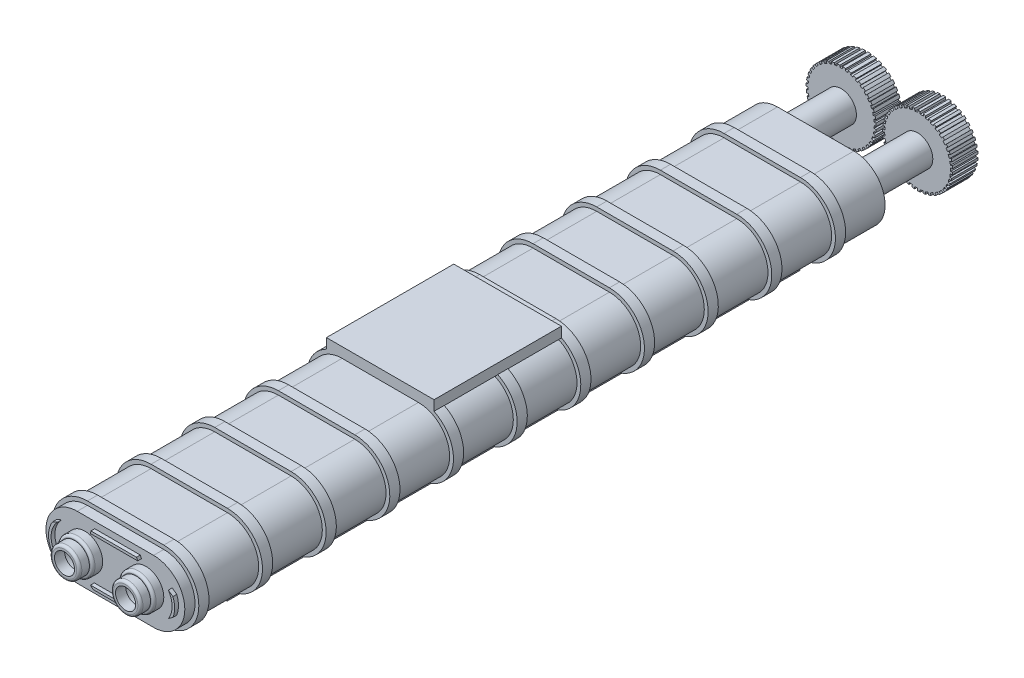
SolidWorks part; units mm, degrees
ref_plane "Front Plane" through (0, 0, 0) normal (0, 0, 1) x (1, 0, 0)
ref_plane "Top Plane" through (0, 0, 0) normal (0, 1, 0) x (1, 0, 0)
ref_plane "Right Plane" through (0, 0, 0) normal (1, 0, 0) x (0, 0, -1)
sketch "Sketch1" plane through (0, 0, 0) normal (0, 0, 1) x (1, 0, 0)
  line L0 (-67.9195, 0) -> (-44.5141, 0) construction
  line L1 (-20, 24.5141) -> (40, 24.5141)
  line L2 (-20, -24.5141) -> (40, -24.5141)
  arc A0 (-20, 24.5141) -> (-20, -24.5141) centre (-20, 0) ccw
  arc A1 (40, -24.5141) -> (40, 24.5141) centre (40, 0) ccw
  dimension "D2" = 49.0283
  dimension "D1" = 60
extrude "Boss-Extrude2" add sketch "Sketch1" along normal mid plane 550
sketch "Sketch4" plane through (0, 0, 0) normal (0, 0, 1) x (1, 0, 0)
  line L0 (27.6992, -24.3343) -> (47.6817, -24.3343)
  line L1 (-27.1587, -24.3343) -> (27.6992, -24.3343)
  line L2 (-27.1587, -24.3343) -> (-27.1587, -27.8343)
  line L3 (-27.1587, -27.8343) -> (27.6992, -27.8343)
  line L4 (47.6817, -24.3343) -> (47.6817, -27.8343)
  line L5 (47.6817, -27.8343) -> (27.6992, -27.8343)
  dimension "D1" = 3.5
extrude "Boss-Extrude3" add sketch "Sketch4" along normal mid plane 450
sketch "Sketch5" plane through (0, 0, -275) normal (0, 0, -1) x (-1, 0, 0)
  circle A0 centre (-40, 0) radius 11.9712
  circle A1 centre (20, 0) radius 11.9712
extrude "Boss-Extrude4" add sketch "Sketch5" along normal blind 50
sketch "Sketch6" plane through (0, 0, -325) normal (0, 0, -1) x (-1, 0, 0)
  circle A0 centre (-40, 0) radius 27.5
  circle A1 centre (20, 0) radius 27.5
  dimension "D1" = 55
  dimension "D2" = 55
extrude "Boss-Extrude5" add sketch "Sketch6" along normal blind 20
sketch "Sketch7" plane through (0, 0, -345) normal (0, 0, -1) x (-1, 0, 0)
  line L1 (-44.5029, 28.9828) -> (-42.0986, 28.9828)
  line L2 (-44.5029, 28.9828) -> (-44.5029, 25.6196)
  line L3 (-44.5029, 25.6196) -> (-42.0986, 25.6196)
  line L4 (-42.0986, 28.9828) -> (-42.0986, 25.6196)
  line L5 (-44.5029, 28.9828) -> (-42.0986, 25.6196) construction
  line L6 (-44.5029, 25.6196) -> (-42.0986, 28.9828) construction
  circle A0 centre (-40, 0) radius 27.5 construction
  point P0 (-43.3007, 27.3012)
extrude "Cut-Extrude1" cut sketch "Sketch7" against normal up to surface (20 mm away) up to face at (12.5, 0, -325)
pattern_circular "CirPattern1" count 39 over 360 about axis through (40, 0, -345) along (0, 0, -1) of "Cut-Extrude1"
sketch "Sketch8" plane through (0, 0, -345) normal (0, 0, -1) x (-1, 0, 0)
  line L1 (19, 29) -> (21, 29)
  line L2 (19, 29) -> (19, 26)
  line L3 (19, 26) -> (21, 26)
  line L4 (21, 29) -> (21, 26)
  line L5 (19, 29) -> (21, 26) construction
  line L6 (19, 26) -> (21, 29) construction
  circle A0 centre (20, 0) radius 27.5 construction
  point P0 (20, 27.5)
  dimension "D1" = 3
  dimension "D2" = 2
extrude "Cut-Extrude2" cut sketch "Sketch8" against normal up to surface (20 mm away) up to face at (-47.5, 0, -325)
pattern_circular "CirPattern2" count 39 over 360 about axis through (-20, 0, -345) along (0, 0, -1) of "Cut-Extrude2"
sketch "Sketch10" plane through (0, 0, 275) normal (0, 0, 1) x (1, 0, 0)
  line L0 (-20, -27.5141) -> (40, -27.5141)
  line L1 (40, 27.5141) -> (-20, 27.5141)
  line L2 (-20, -24.5141) -> (40, -24.5141)
  line L3 (40, 24.5141) -> (-20, 24.5141)
  line L4 (-20, -24.5141) -> (40, -24.5141)
  line L5 (40, 24.5141) -> (-20, 24.5141)
  arc A0 (-20, 27.5141) -> (-20, -27.5141) centre (-20, 0) ccw
  arc A1 (40, -27.5141) -> (40, 27.5141) centre (40, 0) ccw
  arc A2 (-20, 24.5141) -> (-20, -24.5141) centre (-20, 0) ccw
  arc A3 (40, -24.5141) -> (40, 24.5141) centre (40, 0) ccw
  arc A4 (-20, 24.5141) -> (-20, -24.5141) centre (-20, 0) ccw
  arc A5 (40, -24.5141) -> (40, 24.5141) centre (40, 0) ccw
  dimension "D1" = 0
  dimension "D2" = 3
extrude "Boss-Extrude8" add sketch "Sketch10" against normal blind 8 from offset 8 offset against normal yes
pattern_linear "LPattern2" count 11 spacing 50 along (0, 0, -1) of "Boss-Extrude8"
sketch "Sketch11" plane through (0, 0, 275) normal (0, 0, 1) x (1, 0, 0)
  line L0 (-4.5849, -19.5141) -> (28.5455, -19.5141)
  line L1 (29.5434, 19.5141) -> (-6.2358, 19.5141)
  line L2 (-6.2358, 19.5141) -> (-6.5849, 17.5141)
  line L3 (29.5434, 19.5141) -> (30.5455, 17.5141)
  line L4 (-6.5849, -17.5141) -> (-4.5849, -19.5141)
  line L5 (30.5455, -17.5141) -> (28.5455, -19.5141)
  line L6 (30.5455, 17.5141) -> (-6.5849, 17.5141)
  line L7 (-6.5849, -17.5141) -> (30.5455, -17.5141)
  line L8 (-36.4052, 10.5675) -> (-32.0977, 12.6645)
  line L9 (-54.6482, 0) -> (72.6609, 0) construction
  line L10 (9.0064, 0) -> (9.0064, 40.5339) construction
  line L11 (-36.4052, -10.5675) -> (-32.0977, -12.6645)
  line L12 (58.1815, 7.0876) -> (54.6013, 9.6719)
  line L13 (58.1815, -7.0876) -> (54.6013, -9.6719)
  line L14 (40, 17.5141) -> (-20, 17.5141) construction
  line L15 (40, 19.5141) -> (-20, 19.5141) construction
  line L16 (-20, -19.5141) -> (40, -19.5141) construction
  line L17 (-20, -17.5141) -> (40, -17.5141) construction
  arc A0 (-36.4052, 10.5675) -> (-36.4052, -10.5675) centre (-20, 0) ccw
  arc A1 (58.1815, -7.0876) -> (58.1815, 7.0876) centre (40, 0) ccw
  arc A2 (-20, 19.5141) -> (-20, -19.5141) centre (-20, 0) ccw construction
  arc A3 (-20, 17.5141) -> (-20, -17.5141) centre (-20, 0) ccw construction
  arc A4 (40, -19.5141) -> (40, 19.5141) centre (40, 0) ccw construction
  arc A5 (40, -17.5141) -> (40, 17.5141) centre (40, 0) ccw construction
  arc A6 (-32.0977, 12.6645) -> (-32.0977, -12.6645) centre (-20, 0) ccw
  arc A7 (54.6013, -9.6719) -> (54.6013, 9.6719) centre (40, 0) ccw
  dimension "D3" = 2
extrude "Boss-Extrude9" add sketch "Sketch11" along normal blind 3
sketch "Sketch12" plane through (0, 0, 275) normal (0, 0, 1) x (1, 0, 0)
  line L0 (10, 27.5141) -> (10, -39.6147) construction
  line L1 (40, 27.5141) -> (-20, 27.5141) construction
  circle A0 centre (-14, 0) radius 14
  circle A1 centre (34, 0) radius 14
  circle A2 centre (-14, 0) radius 11.6181
  circle A3 centre (34, 0) radius 11.6181
  dimension "D1" = 28
  dimension "D2" = 24
  dimension "D3" = 24
extrude "Boss-Extrude10" add sketch "Sketch12" along normal blind 8
sketch "Sketch13" plane through (0, 0, 283) normal (0, 0, 1) x (1, 0, 0)
  circle A0 centre (-14, 0) radius 11.6181
  circle A1 centre (-14, 0) radius 7.8974
  circle A2 centre (34, 0) radius 11.6181
  circle A3 centre (34, 0) radius 7.8974
extrude "Boss-Extrude11" add sketch "Sketch13" along normal blind 8 separate body
fillet "Fillet3" radius 2 2 edges at (0, 0, 283) (48, 0, 283)
fillet "Fillet4" radius 2 1 edges at (45.6181, 0, 291)
fillet "Fillet5" radius 2 1 edges at (-2.3819, 0, 291)
sketch "Sketch14" plane through (0, 24.5141, 0) normal (0, 1, 0) x (1, 0, 0)
  line L0 (40, -17) -> (-20, -17) construction
  line L1 (-32.2571, 33) -> (52.2571, 33)
  line L2 (-32.2571, 33) -> (-32.2571, -67)
  line L3 (-32.2571, -67) -> (52.2571, -67)
  line L4 (52.2571, 33) -> (52.2571, -67)
  line L5 (-32.2571, 33) -> (52.2571, -67) construction
  line L6 (-32.2571, -67) -> (52.2571, 33) construction
  line L7 (40, -67) -> (64.5141, -67) construction
  point P0 (10, -17)
extrude "Boss-Extrude12" add sketch "Sketch14" along normal blind 8
